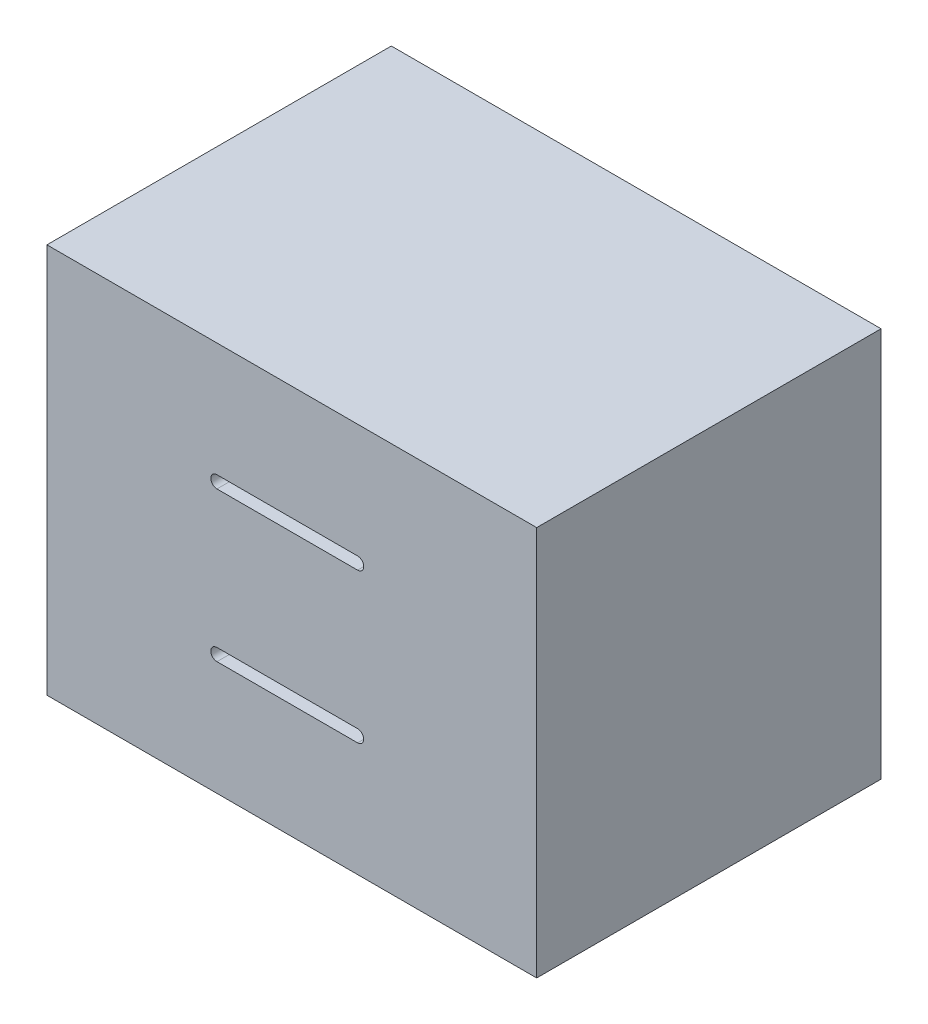
SolidWorks part; units mm, degrees
ref_plane "Front Plane" through (0, 0, 0) normal (0, 0, 1) x (1, 0, 0)
ref_plane "Top Plane" through (0, 0, 0) normal (0, 1, 0) x (1, 0, 0)
ref_plane "Right Plane" through (0, 0, 0) normal (1, 0, 0) x (0, 0, -1)
sketch "Sketch1" plane through (0, 0, 0) normal (0, 1, 0) x (1, 0, 0)
  line L1 (-26.9, -18.915) -> (26.9, -18.915)
  line L2 (-26.9, -18.915) -> (-26.9, 18.915)
  line L3 (-26.9, 18.915) -> (26.9, 18.915)
  line L4 (26.9, -18.915) -> (26.9, 18.915)
  line L5 (-26.9, -18.915) -> (26.9, 18.915) construction
  line L6 (-26.9, 18.915) -> (26.9, -18.915) construction
  point P0 (0, 0)
  dimension "D1" = 53.8
  dimension "D2" = 37.83
extrude "Boss-Extrude1" add sketch "Sketch1" along normal blind 42.85
sketch "Sketch2" plane through (0, 0, -18.915) normal (0, 0, -1) x (-1, 0, 0)
  line L0 (-7.225, 29.64) -> (8.225, 29.64) construction
  line L1 (-7.225, 30.315) -> (8.225, 30.315)
  line L2 (-7.225, 28.965) -> (8.225, 28.965)
  line L3 (-7.9, 42.85) -> (-7.9, 29.64) construction
  line L4 (-26.9, 42.85) -> (26.9, 42.85) construction
  line L5 (8.9, 29.64) -> (8.9, 42.85) construction
  line L6 (-26.9, 42.85) -> (-26.9, 0) construction
  line L7 (26.9, 42.85) -> (26.9, 0) construction
  line L8 (-7.225, 13.21) -> (8.225, 13.21) construction
  line L9 (-7.225, 13.885) -> (8.225, 13.885)
  line L10 (-7.225, 12.535) -> (8.225, 12.535)
  line L11 (0.5, 13.21) -> (0.5, 29.64) construction
  line L12 (0.5, 21.425) -> (-26.9, 21.425) construction
  arc A0 (-7.225, 30.315) -> (-7.225, 28.965) centre (-7.225, 29.64) ccw
  arc A1 (8.225, 28.965) -> (8.225, 30.315) centre (8.225, 29.64) ccw
  arc A2 (-7.225, 13.885) -> (-7.225, 12.535) centre (-7.225, 13.21) ccw
  arc A3 (8.225, 12.535) -> (8.225, 13.885) centre (8.225, 13.21) ccw
  point P2 (0.5, 29.64)
  point P19 (0.5, 13.21)
  dimension "D1" = 19
  dimension "D2" = 1.35
  dimension "D3" = 18
  dimension "D4" = 16.43
extrude "Cut-Extrude1" cut sketch "Sketch2" against normal blind 2
ref_plane "Plane1" through (0, 0, 0) normal (0, 0, -1) x (-1, 0, 0)
mirror "Mirror1" about plane through (0, 0, 0) normal (0, 0, -1) of "Cut-Extrude1"
